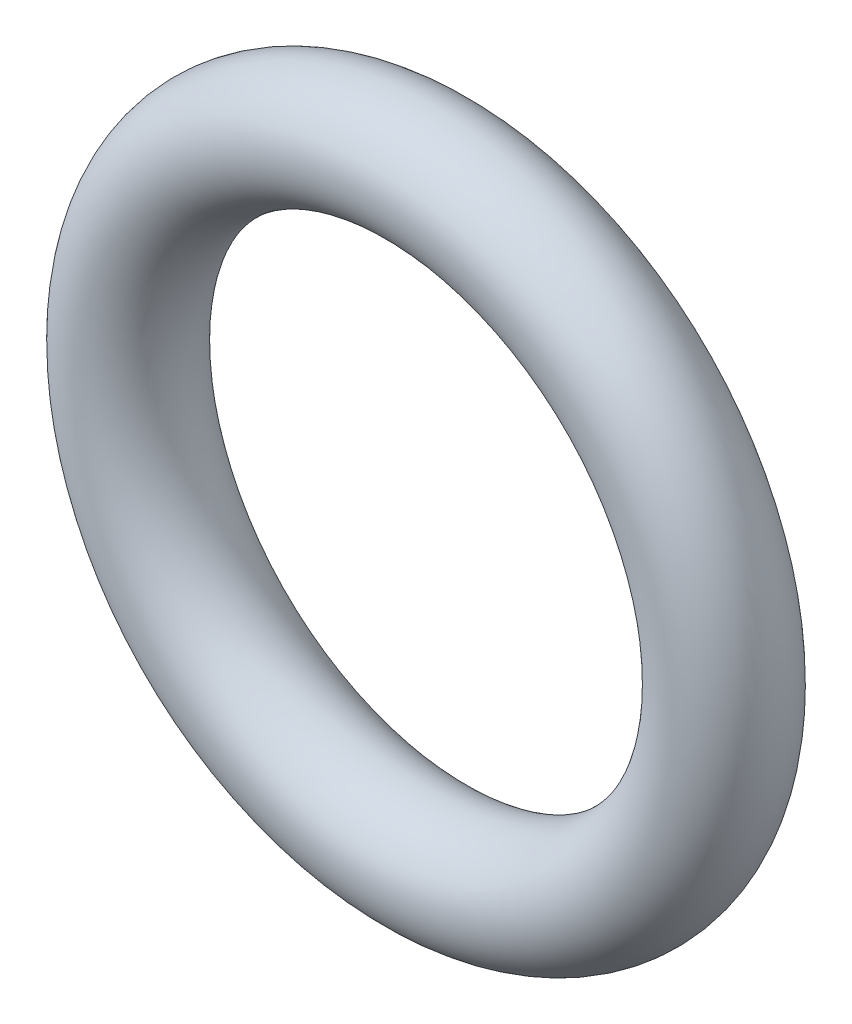
SolidWorks part; units mm, degrees
ref_plane "Front" through (0, 0, 0) normal (0, 0, 1) x (1, 0, 0)
ref_plane "Top" through (0, 0, 0) normal (0, 1, 0) x (1, 0, 0)
ref_plane "Right" through (0, 0, 0) normal (1, 0, 0) x (0, 0, -1)
sketch "Sketch1" plane through (0, 0, 0) normal (0, 0, 1) x (1, 0, 0)
  circle A0 centre (0, 0) radius 3.75
  dimension "d1" = 7.5
sketch "Sketch2" plane through (0, 0, 0) normal (0, 1, 0) x (1, 0, 0)
  circle A0 centre (-4.65, 0) radius 0.9
  point P2 (-3.75, 0)
  dimension "d2" = 1.8
sweep "Sweep1" add profiles "Sketch2" path "Sketch1"
ref_axis "Axis1" through (0, 0, -4.6197) along (0, 0, 1)
